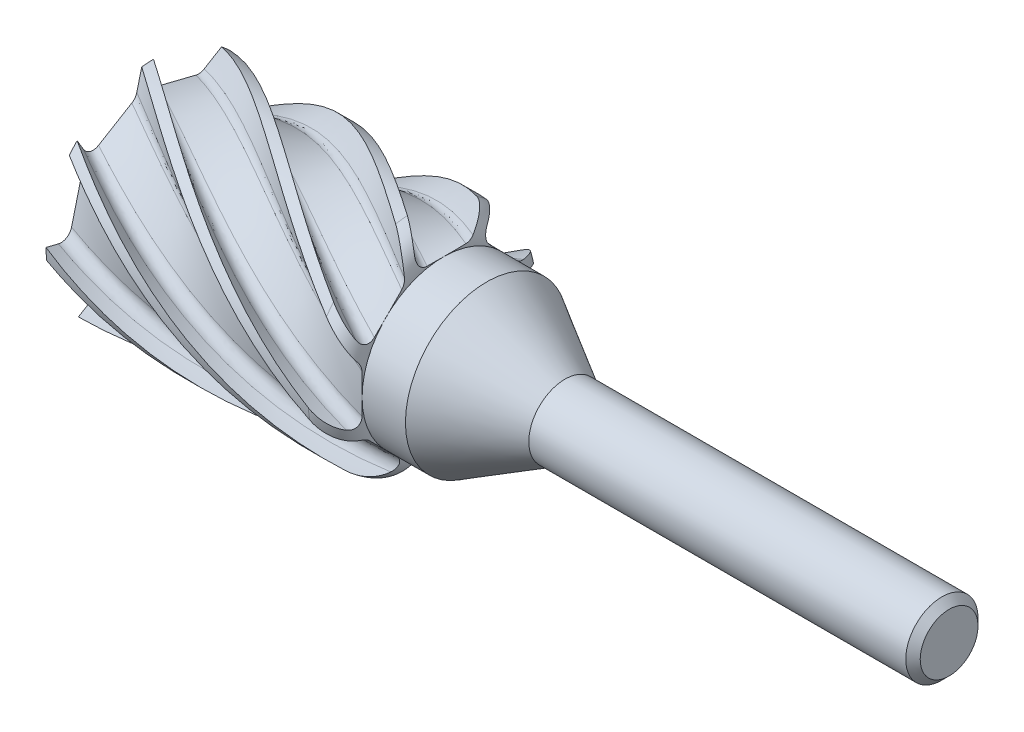
SolidWorks part; units mm, degrees
ref_plane "Front Plane" through (0, 0, 0) normal (0, 0, 1) x (1, 0, 0)
ref_plane "Top Plane" through (0, 0, 0) normal (0, 1, 0) x (1, 0, 0)
ref_plane "Right Plane" through (0, 0, 0) normal (1, 0, 0) x (0, 0, -1)
sketch "Sketch1" plane through (0, 0, 0) normal (0, 0, 1) x (1, 0, 0)
  line L0 (34.925, 0) -> (-34.925, 0) construction
  line L1 (-34.925, 0) -> (-9.525, 0) construction
  line L2 (-9.525, 9.525) -> (-9.525, -9.525) construction
  line L3 (34.925, 3.175) -> (34.925, -3.175) construction
sketch "Sketch2" plane through (0, 0, 0) normal (0, 0, 1) x (1, 0, 0)
  line L0 (34.925, 0) -> (34.925, 3.175)
  line L1 (34.925, 3.175) -> (1.1591, 3.175)
  line L3 (-9.525, 7.1437) -> (-5.715, 7.1437)
  line L4 (-9.525, 9.525) -> (-34.925, 9.525)
  line L5 (-34.925, 9.525) -> (-34.925, 0)
  line L6 (-34.925, 0) -> (34.925, 0)
  line L7 (-9.525, 9.525) -> (-9.525, -9.525) construction
  line L8 (-9.525, 7.1437) -> (-9.525, 3.175) construction
  line L9 (-5.715, 7.1437) -> (1.1591, 3.175)
  line L10 (-9.525, 9.525) -> (-9.525, 7.1437)
  dimension "D1" = 30
  dimension "D2" = 3.81
  dimension "D3" = 2.3813
revolve "Revolve1" add sketch "Sketch2" angle 360 about L6
ref_plane "Plane1" through (-9.525, 0, 0) normal (1, 0, 0) x (0, 0, -1)
split "Split1" trim tools "Plane1" bodies to split 104 resulting bodies 105 106
chamfer "Chamfer1" distance 0.635 angle 45 1 edges at (34.925, 0, 3.175)
sketch "Sketch7" plane through (-34.925, 0, 0) normal (-1, 0, 0) x (0, 0, 1)
  circle A1 centre (0, 0) radius 9.525
  circle A2 centre (0, 0) radius 9.525
  dimension "D1" = 0
ref_plane "Plane2" through (-9.525, 0, 0) normal (1, 0, 0) x (0, 0, -1)
split "Split2" trim tools "Plane2" bodies to split 106 resulting bodies 108
sketch "Sketch3" plane through (-9.525, 0, 0) normal (1, 0, 0) x (0, 0, -1)
  circle A0 centre (0, 0) radius 9.525 construction
  circle A1 centre (0, 0) radius 9.525
curve "Helix/Spiral1" pitch 87.9231 height 28.575 turns 0.325
sketch "Sketch4" plane through (-9.525, 0, 0) normal (1, 0, 0) x (0, 0, -1)
  line L0 (2.6602, 7.4227) -> (7.1438, 11.9062)
  line L1 (-2.3813, 11.9062) -> (2.3813, 11.9062) construction
  line L3 (-1.4287, 7.1437) -> (1.9867, 7.1437)
  line L4 (2.3813, 11.9062) -> (2.3813, 7.1437) construction
  line L5 (-2.3813, 11.9062) -> (2.3813, 7.1437) construction
  line L8 (-2.3813, 11.9062) -> (2.3813, 11.9062)
  line L9 (2.3813, 11.9062) -> (7.1438, 11.9062)
  line L10 (7.1438, 11.9062) -> (2.3813, 11.9062) construction
  line L11 (-2.3813, 11.9062) -> (-2.3813, 8.0962)
  arc A0 (1.9867, 7.1437) -> (2.6602, 7.4227) centre (1.9867, 8.0962) ccw
  arc A1 (-2.3813, 8.0962) -> (-1.4287, 7.1437) centre (-1.4287, 8.0962) ccw
  point P0 (0, 9.525)
  dimension "D2" = 0.9525
  dimension "D1" = 4.7625
sweep "Cut-Sweep1" cut profiles "Sketch4" path "Helix/Spiral1"
sketch "Sketch8" plane through (-9.525, 0, 0) normal (-1, 0, 0) x (0, 0, 1)
  circle A0 centre (0, 0) radius 7.1438 construction
  circle A1 centre (0, 0) radius 7.1438
pattern_circular "CirPattern1" count 8 over 360 about axis through (-9.525, 0, 0) along (-1, 0, 0) of "Cut-Sweep1"
sketch "Sketch10" plane through (0, 0, 0) normal (0, 0, 1) x (1, 0, 0)
  line L0 (-9.525, 7.1437) -> (-9.525, 9.525)
  line L1 (-9.525, 9.525) -> (-11.9062, 9.525)
  line L2 (0, 0) -> (-5.715, 0) construction
  line L3 (-5.715, -7.1438) -> (-5.715, 7.1437) construction
  line L4 (-11.9062, 9.525) -> (-14.2875, 9.525) construction
  arc A0 (-9.525, 7.1437) -> (-11.9062, 9.525) centre (-11.9062, 7.1437) ccw
  dimension "D1" = 2.3813
revolve "Cut-Revolve1" cut sketch "Sketch10" angle 360 about L2
equation "\"D3@Helix/Spiral1\"=\"Head Length@Sketch1\"+.125"
equation "\"D1@Sketch4\"=\"Head Dia@Sketch1\"*.25"
equation "\"D2@Sketch4\"=\"Head Dia@Sketch1\"*.05"
equation "\"D3@Sketch2\"=\"Head Dia@Sketch1\"*.125"
equation "\"D2@Sketch2\"=\"Head Dia@Sketch1\"*.2"
equation "\"D1@Sketch10\"=\"Head Dia@Sketch1\"*.125"
